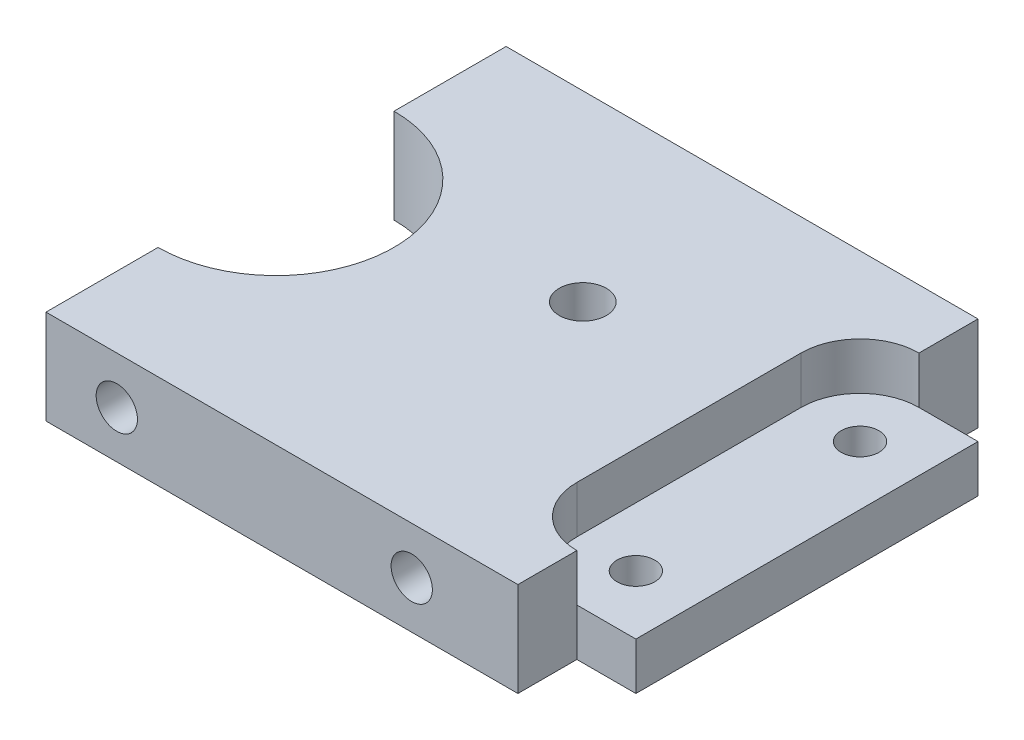
SolidWorks part; units mm, degrees
material "6061 合金"
ref_plane "前视基准面" through (0, 0, 0) normal (0, 0, 1) x (1, 0, 0)
ref_plane "上视基准面" through (0, 0, 0) normal (0, 1, 0) x (1, 0, 0)
ref_plane "右视基准面" through (0, 0, 0) normal (1, 0, 0) x (0, 0, -1)
sketch "草图1" plane through (0, 0, 0) normal (0, 1, 0) x (1, 0, 0)
  line L1 (-22, 15.5) -> (18, 15.5)
  line L2 (-22, 15.5) -> (-22, -23.5)
  line L3 (-22, -23.5) -> (18, -23.5)
  line L4 (18, 15.5) -> (18, -23.5)
  circle A0 centre (0, 0) radius 2
  dimension "D1" = 39
  dimension "D2" = 15.5
  dimension "D3" = 4
  dimension "D4" = 22
  dimension "D5" = 18
extrude "凸台-拉伸1" add sketch "草图1" along normal blind 8
cosmetic thread "装饰螺纹线9" parameters "D2"=5
sketch "草图2" plane through (0, 0, 23.5) normal (0, 0, 1) x (1, 0, 0)
  line L0 (-22, 4) -> (18, 4) construction
  line L1 (-22, 8) -> (-22, 0) construction
  line L2 (18, 8) -> (18, 0) construction
  circle A0 centre (9, 4) radius 1.75
  circle A1 centre (-16, 4) radius 1.75
  dimension "D1" = 25
  dimension "D2" = 34
  dimension "D3" = 3.5
  dimension "D4" = 3.5
extrude "切除-拉伸1" cut sketch "草图2" against normal blind 8
cosmetic thread "装饰螺纹线1" parameters "D1"=8, "D2"=4
cosmetic thread "装饰螺纹线2" parameters "D1"=8, "D2"=4
extrude "切除-拉伸2" cut sketch "草图2<3>" along normal blind 8 from surface starting at face at (-2, 4, -15.5)
sketch "草图2<3>" plane through (0, 0, 23.5) normal (0, 0, 1) x (1, 0, 0) same geometry as "草图2"
cosmetic thread "装饰螺纹线3" parameters "D1"=8, "D2"=4
cosmetic thread "装饰螺纹线4" parameters "D1"=8, "D2"=4
sketch "草图4" plane through (0, 0, 0) normal (0, -1, 0) x (-1, 0, 0)
  line L0 (22, 15.5) -> (22, -23.5) construction
  circle A0 centre (22, -4) radius 10
  dimension "D1" = 20
extrude "切除-拉伸3" cut sketch "草图4" against normal blind 10
sketch "草图6" plane through (0, 8, 0) normal (0, 1, 0) x (1, 0, 0)
  line L0 (18, -13.5) -> (18, 5.5) construction
  line L1 (18, -23.5) -> (18, 15.5) construction
  line L2 (13, -13.5) -> (13, 5.5)
  line L3 (23, -13.5) -> (23, 5.5)
  line L4 (-22, -23.5) -> (18, -23.5) construction
  line L5 (18, 15.5) -> (-22, 15.5) construction
  arc A0 (13, -13.5) -> (23, -13.5) centre (18, -13.5) ccw
  arc A1 (23, 5.5) -> (13, 5.5) centre (18, 5.5) ccw
  point P4 (18, -4)
  dimension "D1" = 5
  dimension "D2" = 10
  dimension "D3" = 10
extrude "切除-拉伸5" cut sketch "草图6" against normal blind 10
sketch "草图7" plane through (0, 0, 0) normal (0, -1, 0) x (1, 0, 0)
  line L0 (13, -5.5) -> (13, 13.5) construction
  line L1 (13, -5.5) -> (13, 13.5)
  line L2 (18, 18.5) -> (23, 18.5)
  line L3 (18, -10.5) -> (23, -10.5)
  line L4 (23, -10.5) -> (23, 18.5)
  arc A0 (13, -5.5) -> (18, -10.5) centre (18, -5.5) ccw construction
  arc A1 (18, 18.5) -> (13, 13.5) centre (18, 13.5) ccw construction
  arc A2 (13, -5.5) -> (18, -10.5) centre (18, -5.5) ccw
  arc A3 (18, 18.5) -> (13, 13.5) centre (18, 13.5) ccw
  circle A4 centre (18, 13.5) radius 1.6
  circle A5 centre (18, -5.5) radius 1.6
  dimension "D1" = 3.2
  dimension "D2" = 5
extrude "凸台-拉伸2" add sketch "草图7" against normal blind 4
cosmetic thread "装饰螺纹线14" parameters "D2"=4
cosmetic thread "装饰螺纹线15" parameters "D2"=4
